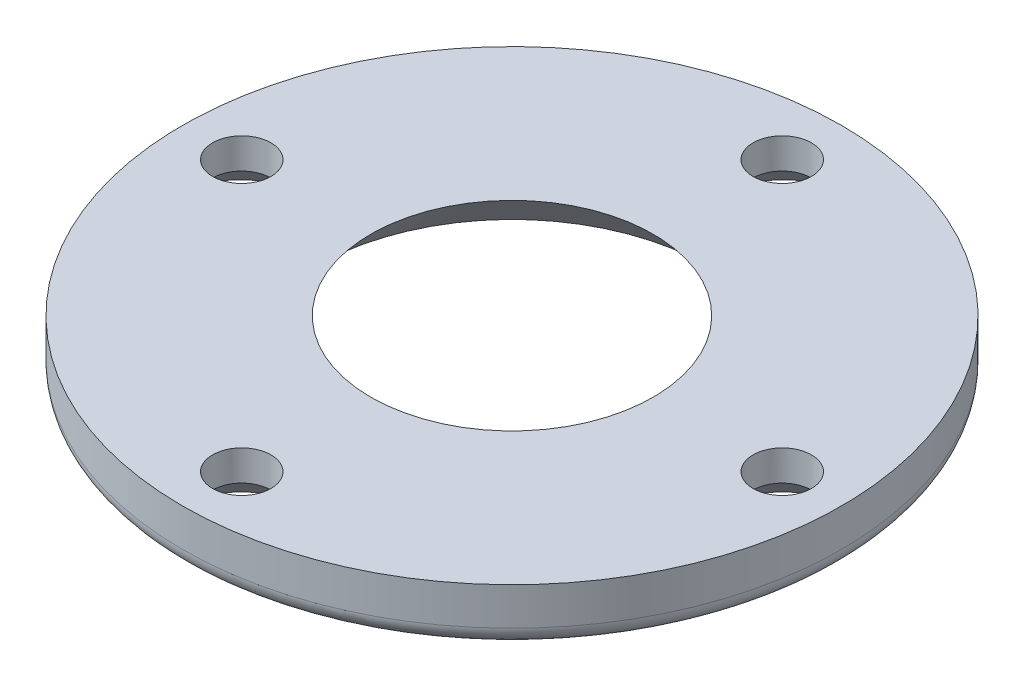
SolidWorks part; units mm, degrees
ref_plane "Front Plane" through (0, 0, 0) normal (0, 0, 1) x (1, 0, 0)
ref_plane "Top Plane" through (0, 0, 0) normal (0, 1, 0) x (1, 0, 0)
ref_plane "Right Plane" through (0, 0, 0) normal (1, 0, 0) x (0, 0, -1)
sketch "Sketch1" plane through (0, 0, 0) normal (0, 1, 0) x (1, 0, 0)
  circle A0 centre (0, 0) radius 17.5
  circle A1 centre (0, 0) radius 7.5
  dimension "D1" = 35
  dimension "D2" = 15
extrude "Boss-Extrude1" add sketch "Sketch1" along normal blind 3
sketch "Sketch3" plane through (0, 0, 0) normal (0, -1, 0) x (1, 0, 0)
  line L0 (0, 0) -> (0, 14.35) construction
  circle A0 centre (0, 14.35) radius 1.55
  dimension "D2" = 3.1
  dimension "D1" = 14.35
extrude "Cut-Extrude1" cut sketch "Sketch3" against normal blind 5
chamfer "Chamfer6" distance 1.38 angle 45 1 edges at (0, 0, 12.8)
pattern_circular "CirPattern2" count 4 over 360 about axis through (0, 0, 0) along (0, 1, 0) of "Chamfer6", "Cut-Extrude1"
chamfer "Chamfer7" distance 3 angle 45 1 edges at (0, 0, 7.5)
fillet "Fillet1" radius 1 1 edges at (0, 0, 17.5)
equation "\"0.2mmmm\"=1"
